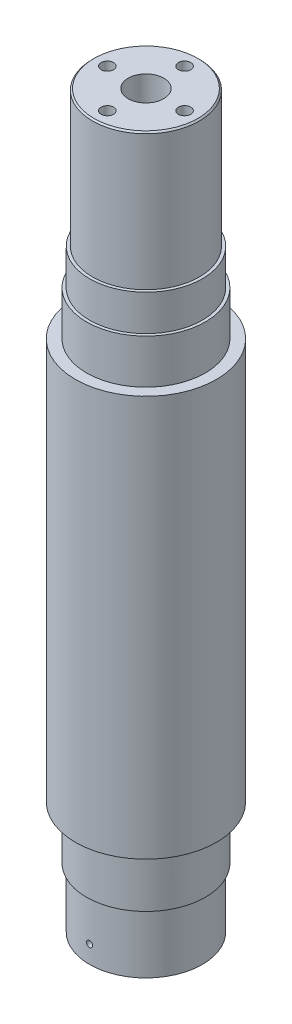
SolidWorks part; units mm, degrees
material "Stainless Steel (ferritic)"
ref_plane "Front" through (0, 0, 0) normal (0, 0, 1) x (1, 0, 0)
ref_plane "Top" through (0, 0, 0) normal (0, 1, 0) x (1, 0, 0)
ref_plane "Right" through (0, 0, 0) normal (1, 0, 0) x (0, 0, -1)
sketch "Sketch1" plane through (0, 0, 0) normal (0, 1, 0) x (1, 0, 0)
  circle A0 centre (0, 0) radius 25
  dimension "D1" = 50
extrude "Boss-Extrude1" add sketch "Sketch1" along normal blind 95 and the other way blind 105
sketch "Sketch2" plane through (0, 95, 0) normal (0, 1, 0) x (1, 0, 0)
  circle A0 centre (0, 0) radius 18
  dimension "D1" = 36
extrude "Boss-Extrude2" add sketch "Sketch2" along normal blind 46
ref_plane "Plane1" through (0, 0, -15) normal (0, 0, 1) x (1, 0, 0)
sketch "Sketch8" plane through (0, 0, -15) normal (0, 0, 1) x (1, 0, 0)
  line L0 (0, 122) -> (0, 103) construction
  line L1 (3, 122) -> (3, 103)
  line L2 (-3, 122) -> (-3, 103)
  line L4 (25, 95) -> (-25, 95) construction
  arc A0 (3, 122) -> (-3, 122) centre (0, 122) ccw
  arc A1 (-3, 103) -> (3, 103) centre (0, 103) ccw
  point P2 (0, 112.5)
  dimension "D2" = 3
  dimension "D1" = 17.5
  dimension "D3" = 9.5
extrude "Cut-Extrude1" cut sketch "Sketch8" against normal blind 10
chamfer "Chamfer1" distance 0.5 angle 45 1 edges at (0, 141, 18)
sketch "Sketch9" plane through (0, -105, 0) normal (0, -1, 0) x (1, 0, 0)
  circle A0 centre (0, 0) radius 10
  dimension "D1" = 20
extrude "Cut-Extrude2" cut sketch "Sketch9" against normal blind 30 draft 8
sketch "Sketch10" plane through (0, -105, 0) normal (0, -1, 0) x (1, 0, 0)
  circle A0 centre (0, 0) radius 6.5
  dimension "D1" = 13
extrude "Cut-Extrude3" cut sketch "Sketch10" against normal blind 50
sketch "Sketch11" plane through (0, 141, 0) normal (0, 1, 0) x (1, 0, 0)
  circle A0 centre (0, 0) radius 6
  dimension "D1" = 12
extrude "Cut-Extrude4" cut sketch "Sketch11" against normal through all
hole_wizard "M5x0.8 Tapped Hole1" positions "Sketch13" profile "Sketch15" tap size "M5x0.8" standard "ANSI Metric"
sketch "Sketch13" plane through (0, 141, 0) normal (0, 1, 0) x (1, 0, 0)
  point P0 (0, 13)
  dimension "D1" = 13
sketch "Sketch15" plane through (0, 141, -13) normal (1, 0, 0) x (0, 0, 1)
  line L0 (0, 0) -> (0, 12)
  line L1 (0, 12) -> (2.1, 10.7382)
  line L2 (2.1, 10.7382) -> (2.1, 0)
  line L5 (2.1, 0) -> (0, 0)
  line L10 (0, 12) -> (-2.1, 10.7382) construction
  line L11 (0, -6.35) -> (0, 107.95) construction
  dimension "Tap Drill Dia." = 4.2
  dimension "Tap Drill Depth" = 12
  dimension "Drill Angle" = 118
cosmetic thread "Hole Thread1" parameters "D1"=10, "D2"=5
pattern_circular "CirPattern1" count 4 over 360 about axis through (0, -105, 0) along (0, 1, 0) of "M5x0.8 Tapped Hole1" reverse direction yes
cosmetic thread "Hole Thread2" parameters "D1"=10, "D2"=5
cosmetic thread "Hole Thread3" parameters "D1"=10, "D2"=5
cosmetic thread "Hole Thread4" parameters "D1"=10, "D2"=5
hole_wizard "M2.5x0.45 Tapped Hole1" positions "Sketch19" profile "Sketch20" tap size "M2.5x0.45" standard "ANSI Metric"
sketch "Sketch19" plane through (0, -105, 0) normal (0, -1, 0) x (-1, 0, 0)
  point P0 (-12.2, 0)
  dimension "D1" = 12.2
sketch "Sketch20" plane through (12.2, -105, 0) normal (1, 0, 0) x (0, 0, -1)
  line L0 (0, 0) -> (0, 9.35)
  line L1 (0, 9.35) -> (1.025, 8.7341)
  line L2 (1.025, 8.7341) -> (1.025, 0)
  line L5 (1.025, 0) -> (0, 0)
  line L10 (0, 9.35) -> (-1.025, 8.7341) construction
  line L11 (0, -6.35) -> (0, 107.95) construction
  dimension "Tap Drill Dia." = 2.05
  dimension "Tap Drill Depth" = 9.35
  dimension "Drill Angle" = 118
cosmetic thread "Hole Thread7" parameters "D1"=8, "D2"=2.5
mirror "Mirror2" about plane through (0, 0, 0) normal (1, 0, 0) of "M2.5x0.45 Tapped Hole1"
cosmetic thread "Hole Thread8" parameters "D1"=8, "D2"=2.5
sketch "Sketch21" plane through (0, -1, 0) normal (0, 1, 0) x (1, 0, 0)
  circle A0 centre (0, 0) radius 20
  circle A1 centre (0, 0) radius 25
  dimension "D1" = 40
  dimension "D2" = 50
extrude "Cut-Extrude6" cut sketch "Sketch21" along normal blind 27 from offset 69
extrude "Cut-Extrude7" cut sketch "Sketch21<2>" against normal blind 39 from offset 66 offset against normal yes
sketch "Sketch21<2>" plane through (0, -1, 0) normal (0, 1, 0) x (1, 0, 0) same geometry as "Sketch21"
sketch "Sketch23" plane through (0, 95, 0) normal (0, 1, 0) x (1, 0, 0)
  circle A0 centre (0, 0) radius 25
  circle A1 centre (0, 0) radius 23.75
  dimension "D1" = 47.5
  dimension "D2" = 50
extrude "Cut-Extrude8" cut sketch "Sketch23" against normal blind 135 from offset 27 offset against normal yes
sketch "Sketch24" plane through (0, -105, 0) normal (0, -1, 0) x (1, 0, 0)
  circle A0 centre (0, 0) radius 19
  circle A1 centre (0, 0) radius 20
  dimension "D1" = 38
  dimension "D2" = 40
extrude "Cut-Extrude9" cut sketch "Sketch24" against normal blind 20.1
hole_wizard "M2.5x0.45 Tapped Hole2" positions "3DSketch1" profile "Sketch22" tap size "M2.5x0.45" standard "ANSI Metric"
sketch3d "3DSketch1"
  point P0 (0, -99, -19)
  point P2 (0, -99, 19)
  point P3 (0, 0, 0)
  point P7 (0, 0, 0)
  point P8 (0, 0, 0)
  dimension "D1" = 6
  dimension "D2" = 6
sketch "Sketch22" plane through (0, -99, -19) normal (1, 0, 0) x (0, 1, 0)
  line L0 (0, 0) -> (0, 5.6159)
  line L1 (0, 5.6159) -> (1.025, 5)
  line L2 (1.025, 5) -> (1.025, 0)
  line L5 (1.025, 0) -> (0, 0)
  line L10 (0, 5.6159) -> (-1.025, 5) construction
  line L11 (0, -6.35) -> (0, 107.95) construction
  dimension "Tap Drill Dia." = 2.05
  dimension "Tap Drill Depth" = 5
  dimension "Drill Angle" = 118
cosmetic thread "Hole Thread9" parameters "D1"=5, "D2"=2.5
cosmetic thread "Hole Thread10" parameters "D1"=5, "D2"=2.5
sketch "Sketch25" plane through (0, 95, 0) normal (0, 1, 0) x (1, 0, 0)
  circle A0 centre (0, 0) radius 19
  circle A1 centre (0, 0) radius 20
  dimension "D1" = 38
  dimension "D2" = 40
extrude "Cut-Extrude10" cut sketch "Sketch25" against normal blind 12.1
